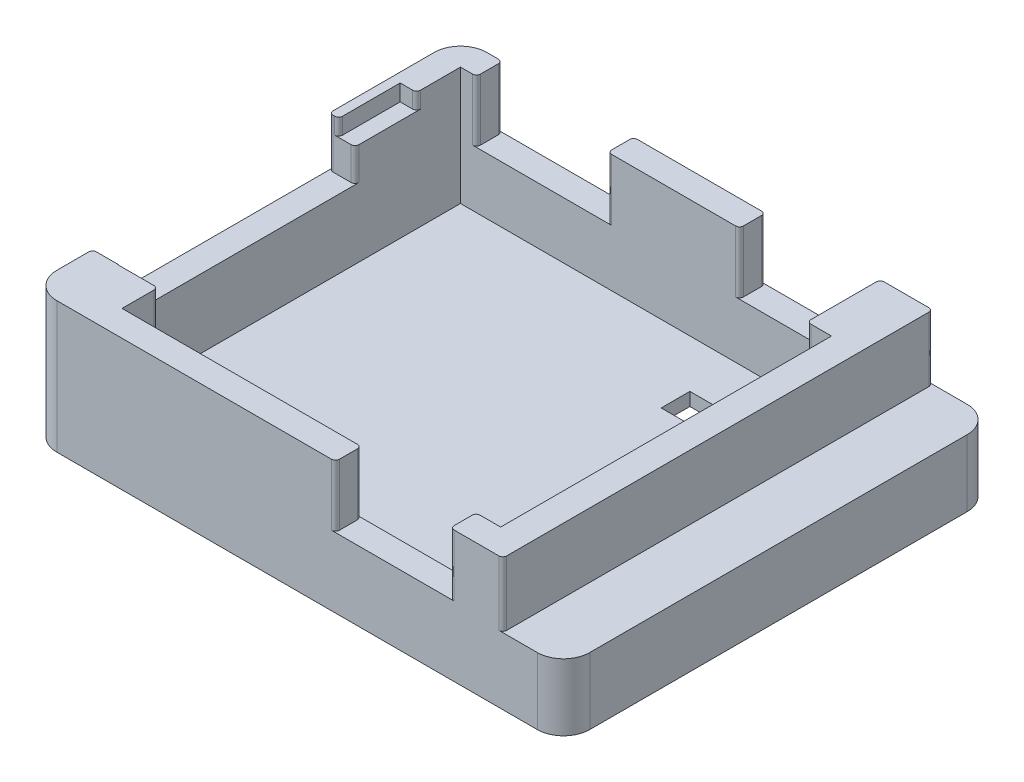
SolidWorks part; units mm, degrees
ref_plane "Front Plane" through (0, 0, 0) normal (0, 0, 1) x (1, 0, 0)
ref_plane "Top Plane" through (0, 0, 0) normal (0, 1, 0) x (1, 0, 0)
ref_plane "Right Plane" through (0, 0, 0) normal (1, 0, 0) x (0, 0, -1)
sketch "Sketch1" plane through (0, 0, 0) normal (0, 1, 0) x (1, 0, 0)
  line L1 (0, 0) -> (103.124, 0)
  line L2 (0, 0) -> (0, 83.185)
  line L3 (0, 83.185) -> (103.124, 83.185)
  line L4 (103.124, 0) -> (103.124, 83.185)
  dimension "D1" = 103.124
  dimension "D2" = 83.185
extrude "Boss-Extrude1" add sketch "Sketch1" along normal blind 25.4
sketch "Sketch2" plane through (0, 25.4, 0) normal (0, 1, 0) x (1, 0, 0)
  line L0 (0, 83.185) -> (0, 0) construction
  line L1 (5, 78.185) -> (81.2, 78.185)
  line L2 (5, 78.185) -> (5, 11.9253)
  line L3 (12.7, 5) -> (85.9625, 5)
  line L4 (85.9625, 69.0118) -> (85.9625, 5)
  line L5 (103.124, 83.185) -> (0, 83.185) construction
  line L6 (0, 0) -> (103.124, 0) construction
  line L7 (5, 11.9253) -> (12.7, 11.9253)
  line L8 (12.7, 11.9253) -> (12.7, 5)
  line L9 (81.2, 78.185) -> (81.2, 69.0118)
  line L10 (81.2, 69.0118) -> (85.9625, 69.0118)
  dimension "D1" = 5
  dimension "D2" = 5
  dimension "D3" = 80.9625
  dimension "D4" = 5
  dimension "D5" = 11.9253
  dimension "D6" = 12.7
  dimension "D7" = 76.2
  dimension "D8" = 14.1732
extrude "Cut-Extrude1" cut sketch "Sketch2" against normal blind 22.86
sketch "Sketch3" plane through (0, 25.4, 0) normal (0, 1, 0) x (1, 0, 0)
  line L0 (0, 0) -> (103.124, 0) construction
  line L1 (103.124, 83.185) -> (91.3765, 83.185)
  line L2 (103.124, 83.185) -> (103.124, 0)
  line L3 (103.124, 0) -> (91.3765, 0)
  line L4 (91.3765, 83.185) -> (91.3765, 0)
  dimension "D1" = 11.7475
extrude "Cut-Extrude2" cut sketch "Sketch3" against normal blind 12.4841
sketch "Sketch4" plane through (0, 0, -83.185) normal (0, 0, -1) x (-1, 0, 0)
  line L0 (-91.3765, 25.4) -> (0, 25.4) construction
  line L1 (-81.2165, 25.4) -> (-58.9915, 25.4)
  line L2 (-81.2165, 25.4) -> (-81.2165, 13.4937)
  line L3 (-81.2165, 13.4937) -> (-58.9915, 13.4937)
  line L4 (-58.9915, 25.4) -> (-58.9915, 13.4937)
  line L5 (-91.3765, 12.9159) -> (-91.3765, 25.4) construction
  dimension "D1" = 10.16
  dimension "D2" = 22.225
  dimension "D3" = 11.9062
extrude "Cut-Extrude3" cut sketch "Sketch4" against normal blind 127
sketch "Sketch5" plane through (0, 0, -83.185) normal (0, 0, -1) x (-1, 0, 0)
  line L0 (-58.9915, 25.4) -> (0, 25.4) construction
  line L1 (-8.1026, 25.4) -> (-33.5026, 25.4)
  line L2 (-8.1026, 25.4) -> (-8.1026, 13.4938)
  line L3 (-8.1026, 13.4938) -> (-33.5026, 13.4937)
  line L4 (-33.5026, 25.4) -> (-33.5026, 13.4937)
  line L5 (0, 25.4) -> (0, 0) construction
  dimension "D1" = 25.4
  dimension "D2" = 8.1026
  dimension "D3" = 11.9062
extrude "Cut-Extrude4" cut sketch "Sketch5" against normal blind 5.08
sketch "Sketch6" plane through (0, 0, 0) normal (-1, 0, 0) x (0, 0, 1)
  line L0 (-83.185, 25.4) -> (0, 25.4) construction
  line L1 (-12.0015, 25.4) -> (-57.785, 25.4)
  line L2 (-12.0015, 25.4) -> (-12.0015, 15.875)
  line L3 (-12.0015, 15.875) -> (-57.785, 15.875)
  line L4 (-57.785, 25.4) -> (-57.785, 15.875)
  line L5 (-83.185, 25.4) -> (-83.185, 0) construction
  dimension "D1" = 45.7835
  dimension "D2" = 9.525
  dimension "D3" = 25.4
extrude "Cut-Extrude5" cut sketch "Sketch6" against normal blind 5.08
sketch "Sketch7" plane through (0, 25.4, 0) normal (0, 1, 0) x (1, 0, 0)
  line L1 (5, 57.785) -> (1.825, 57.785)
  line L2 (5, 57.785) -> (5, 69.6912)
  line L3 (5, 69.6912) -> (1.825, 69.6912)
  line L4 (1.825, 57.785) -> (1.825, 69.6912)
  dimension "D1" = 11.9062
  dimension "D2" = 3.175
extrude "Cut-Extrude6" cut sketch "Sketch7" against normal blind 3.175
sketch "Sketch8" plane through (0, 0, 0) normal (0, -1, 0) x (1, 0, 0)
  line L1 (58.674, -63.3413) -> (69.7865, -63.3413)
  line L2 (58.674, -63.3413) -> (58.674, -68.8975)
  line L3 (58.674, -68.8975) -> (69.7865, -68.8975)
  line L4 (69.7865, -63.3413) -> (69.7865, -68.8975)
  line L6 (103.124, -83.185) -> (0, -83.185) construction
  line L8 (103.124, 0) -> (103.124, -83.185) construction
  dimension "D1" = 33.3375
  dimension "D2" = 5.5562
  dimension "D3" = 14.2875
  dimension "D4" = 11.1125
extrude "Cut-Extrude7" cut sketch "Sketch8" against normal blind 5.08
fillet "Fillet1" radius 5.08 4 edges at (103.124, 6.4579, -83.185) (103.124, 6.4579, 0) (0, 12.7, 0) (0, 12.7, -83.185)
fillet "Fillet2" radius 0.762 20 edges at (91.3765, 19.1579, 0) (81.2165, 19.4469, 0) (81.2165, 19.4469, -5) (58.9915, 19.4469, 0) (58.9915, 19.4469, -5) (12.7, 13.97, -11.9253) (0, 20.6375, -12.0015) (0, 20.6375, -57.785) (91.3765, 19.1579, -83.185) (81.2165, 19.4469, -69.0118) (81.2165, 19.4469, -83.185) (58.9915, 19.4469, -83.185) (58.9915, 19.4469, -78.185) (33.5026, 19.4469, -78.185) (33.5026, 19.4469, -83.185) (8.1026, 19.4469, -83.185) (8.1026, 19.4469, -78.185) (1.825, 23.8125, -57.785) (5, 23.8125, -69.6912) (5, 19.05, -57.785)
